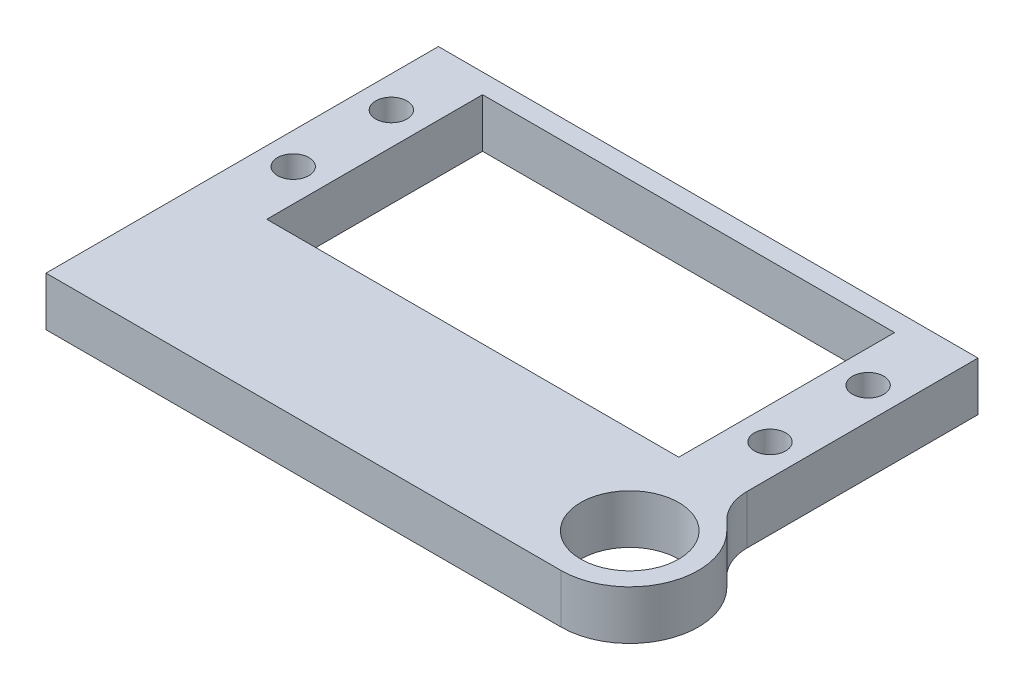
SolidWorks part; units mm, degrees
ref_plane "Front Plane" through (0, 0, 0) normal (0, 0, 1) x (1, 0, 0)
ref_plane "Top Plane" through (0, 0, 0) normal (0, 1, 0) x (1, 0, 0)
ref_plane "Right Plane" through (0, 0, 0) normal (1, 0, 0) x (0, 0, -1)
ref_axis "X" through (-88.99, 0, 0) along (1, 0, 0)
ref_axis "Y" through (0, 55, 0) along (0, -1, 0)
ref_axis "Z" through (0, 0, -88.99) along (0, 0, 1)
sketch "Sketch1" plane through (0, 0, 0) normal (0, 1, 0) x (1, 0, 0)
  line L0 (4.9497, 4.9497) -> (3.9645, 5.935)
  line L1 (2.5, 9.4706) -> (2.5, 33)
  line L2 (2.5, 33) -> (-52.5, 33)
  line L3 (-52.5, 33) -> (-52.5, -7)
  line L4 (0, -7) -> (-52.5, -7)
  line L5 (-25, 20) -> (-25, 33) construction
  line L6 (-49.3, 25) -> (-0.7, 25) construction
  line L7 (-49.3, 25) -> (-49.3, 15) construction
  line L8 (-49.3, 15) -> (-0.7, 15) construction
  line L9 (-0.7, 25) -> (-0.7, 15) construction
  line L10 (-49.3, 25) -> (-0.7, 15) construction
  line L11 (-49.3, 15) -> (-0.7, 25) construction
  line L13 (-46, 31) -> (-4, 31)
  line L14 (-46, 31) -> (-46, 9)
  line L15 (-46, 9) -> (-4, 9)
  line L16 (-4, 31) -> (-4, 9)
  line L17 (-46, 31) -> (-4, 9) construction
  line L18 (-46, 9) -> (-4, 31) construction
  circle A0 centre (0, 0) radius 5
  arc A1 (0, -7) -> (4.9497, 4.9497) centre (0, 0) ccw
  arc A2 (3.9645, 5.935) -> (2.5, 9.4706) centre (7.5, 9.4706) cw
  circle A3 centre (-0.7, 25) radius 1.6
  circle A4 centre (-0.7, 15) radius 1.6
  circle A5 centre (-49.3, 15) radius 1.6
  circle A6 centre (-49.3, 25) radius 1.6
  point P18 (-25, 20)
  dimension "D1" = 10
  dimension "D2" = 45
  dimension "D3" = 2
  dimension "D4" = 5
  dimension "D5" = 3.2
  dimension "D6" = 42
  dimension "D7" = 22
  dimension "D8" = 48.6
  dimension "D9" = 10
  dimension "D10" = 25
  dimension "D11" = 20
  dimension "D12" = 55
  dimension "D13" = 2
extrude "Boss-Extrude1" add sketch "Sketch1" against normal blind 5 contours L0 A2 L1 L2 L3 L4 A1 A6 A5 A4 A3 L13 L16 L15 L14 A0 region at (-25.5649, 0, -7.8484)
